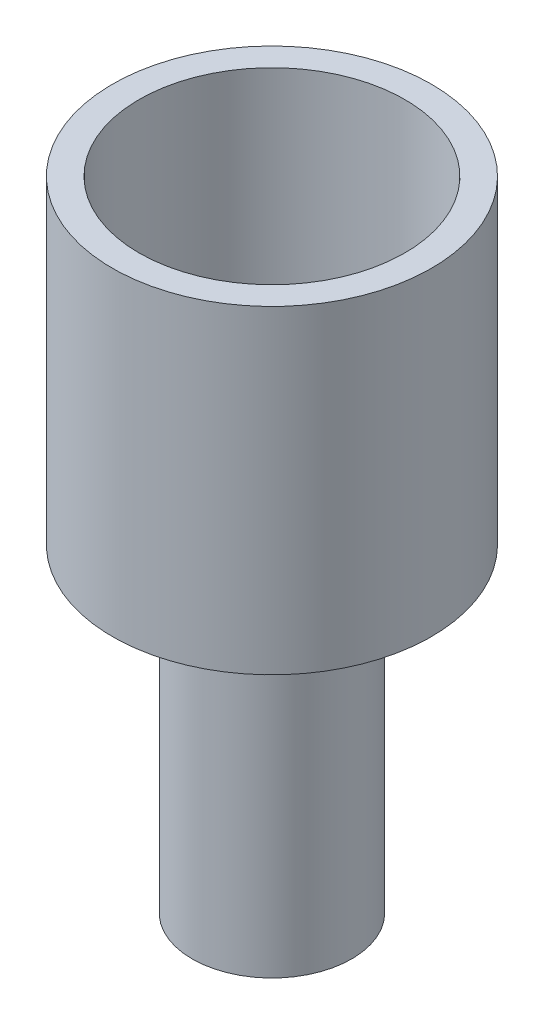
SolidWorks part; units mm, degrees
material "6061-T4 (SS)"
ref_plane "Front Plane" through (0, 0, 0) normal (0, 0, 1) x (1, 0, 0)
ref_plane "Top Plane" through (0, 0, 0) normal (0, 1, 0) x (1, 0, 0)
ref_plane "Right Plane" through (0, 0, 0) normal (1, 0, 0) x (0, 0, -1)
sketch "Sketch1" plane through (0, 0, 0) normal (0, 0, 1) x (1, 0, 0)
  line L0 (-9.525, 19.05) -> (-9.525, 0)
  line L1 (-9.525, 0) -> (-4.7625, 0)
  line L2 (-4.7625, 0) -> (-4.7625, -19.05)
  line L3 (0, -15.8578) -> (0, 15.6451) construction
  dimension "D1" = 9.525
  dimension "D2" = 19.05
  dimension "D3" = 19.05
  dimension "D4" = 19.05
sketch "Sketch2" plane through (0, 0, 0) normal (0, 1, 0) x (1, 0, 0)
  circle A0 centre (0, 0) radius 9.525
  circle A1 centre (0, 0) radius 4.7625
extrude "Boss-Extrude1" add sketch "Sketch2" along normal up to vertex (19.05 mm away) contours A0 A1 | A1 | A1 | A0 region at (-9.2556, 0, 0) region at (0, 0, 0) up to point (-9.525, 19.05, 0)
extrude "Boss-Extrude2" add sketch "Sketch2<3>" against normal up to vertex (19.05 mm away) contours A1 region at (0, 0, 0) up to point (-4.7625, -19.05, 0)
sketch "Sketch2<3>" plane through (0, 0, 0) normal (0, 1, 0) x (1, 0, 0) same geometry as "Sketch2"
sketch "Sketch7" plane through (0, 19.05, 0) normal (0, 1, 0) x (1, 0, 0)
  point P0 (0, 0)
hole_wizard "5/8 (0.625) Diameter Hole1" positions "Sketch7" profile "Sketch6" hole size "5/8" standard "ANSI Inch"
sketch "Sketch6" plane through (0, 19.05, 0) normal (1, 0, 0) x (0, 0, 1)
  line L0 (0, 0) -> (0, 19.05)
  line L1 (0, 19.05) -> (7.9375, 14.2807)
  line L2 (7.9375, 14.2807) -> (7.9375, 0)
  line L5 (7.9375, 0) -> (0, 0)
  line L10 (0, 19.05) -> (-7.9375, 14.2807) construction
  line L11 (0, -6.35) -> (0, 107.95) construction
  dimension "Hole Dia." = 15.875
  dimension "Hole Depth" = 19.05
  dimension "Drill Angle" = 118
sketch "Sketch10" plane through (0, -19.05, 0) normal (0, -1, 0) x (-1, 0, 0)
  point P0 (0, 0)
hole_wizard "1/4 (0.25) Diameter Hole1" positions "Sketch10" profile "Sketch11" hole size "1/4" standard "ANSI Inch" end condition through all
sketch "Sketch11" plane through (0, -19.05, 0) normal (1, 0, 0) x (0, 0, -1)
  line L0 (0, 0) -> (0, 38.1)
  line L1 (0, 38.1) -> (3.175, 38.1)
  line L2 (3.175, 38.1) -> (3.175, 0)
  line L5 (3.175, 0) -> (0, 0)
  line L11 (0, -6.35) -> (0, 107.95) construction
  dimension "Thru Hole Dia." = 6.35
  dimension "Thru Hole Depth" = 38.1
